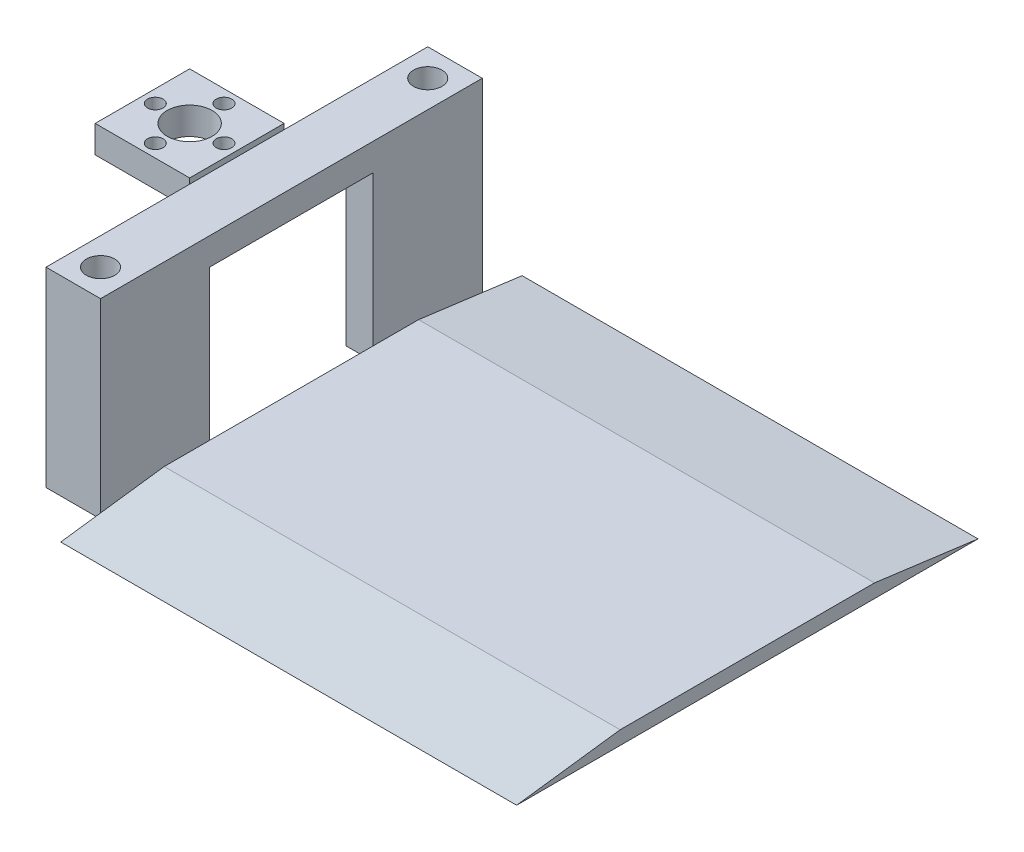
SolidWorks part; units mm, degrees
ref_plane "Front Plane" through (0, 0, 0) normal (0, 0, 1) x (1, 0, 0)
ref_plane "Top Plane" through (0, 0, 0) normal (0, 1, 0) x (1, 0, 0)
ref_plane "Right Plane" through (0, 0, 0) normal (1, 0, 0) x (0, 0, -1)
sketch "Sketch1" plane through (0, 0, 0) normal (0, 1, 0) x (1, 0, 0)
  line L1 (0, 0) -> (106.172, 0)
  line L2 (0, 0) -> (0, 107.442)
  line L3 (0, 107.442) -> (106.172, 107.442)
  line L4 (106.172, 0) -> (106.172, 107.442)
  dimension "D1" = 107.442
  dimension "D2" = 106.172
extrude "Boss-Extrude1" add sketch "Sketch1" along normal blind 3.175
sketch "Sketch3" plane through (0, 0, 0) normal (0, 1, 0) x (1, 0, 0)
  line L0 (0, 53.721) -> (106.172, 53.721) construction
  line L5 (-12.7, 85.471) -> (0, 85.471)
  line L6 (-12.7, 85.471) -> (-12.7, 98.171)
  line L7 (-12.7, 98.171) -> (0, 98.171)
  line L8 (0, 85.471) -> (0, 98.171)
  line L9 (-12.7, 85.471) -> (0, 98.171) construction
  line L10 (-12.7, 98.171) -> (0, 85.471) construction
  line L11 (0, 107.442) -> (0, 0) construction
  line L12 (106.172, 0) -> (106.172, 107.442) construction
  line L13 (-12.7, 9.271) -> (0, 21.971) construction
  line L14 (-12.7, 21.971) -> (0, 9.271) construction
  line L15 (0, 21.971) -> (0, 9.271)
  line L16 (-12.7, 9.271) -> (0, 9.271)
  line L17 (-12.7, 21.971) -> (-12.7, 9.271)
  line L18 (-12.7, 21.971) -> (0, 21.971)
  circle A1 centre (-6.35, 91.821) radius 3.302
  circle A2 centre (-6.35, 15.621) radius 3.302
  point P0 (-6.35, 91.821)
  point P21 (-6.35, 15.621)
  dimension "D2" = 6.604
  dimension "D1" = 12.7
  dimension "D3" = 12.7
  dimension "D4" = 76.2
extrude "Boss-Extrude2" add sketch "Sketch3" along normal blind 44.45
sketch "Sketch4" plane through (106.172, 0, 0) normal (1, 0, 0) x (0, 0, -1)
  line L5 (0, 0) -> (24.0965, 3.175)
  line L7 (0, 3.175) -> (107.442, 3.175) construction
  line L8 (24.0965, 3.175) -> (0, 3.175)
  line L9 (0, 3.175) -> (0, 0)
  line L10 (53.721, 3.175) -> (53.721, 0) construction
  line L11 (0, 0) -> (107.442, 0) construction
  line L12 (107.442, 3.175) -> (107.442, 0)
  line L13 (83.3455, 3.175) -> (107.442, 3.175)
  line L14 (107.442, 0) -> (83.3455, 3.175)
extrude "Cut-Extrude1" cut sketch "Sketch4" against normal up to surface (106.172 mm away) up to face at (0, 23.8125, -15.621)
sketch "Sketch6" plane through (0, 0, -85.471) normal (0, 0, 1) x (1, 0, 0)
  line L0 (0, 44.45) -> (0, 2.8949) construction
  line L1 (-12.7, 44.45) -> (0, 44.45)
  line L2 (-12.7, 44.45) -> (-12.7, 38.1)
  line L3 (-12.7, 38.1) -> (0, 38.1)
  line L4 (0, 44.45) -> (0, 38.1)
  dimension "D1" = 6.35
extrude "Boss-Extrude3" add sketch "Sketch6" along normal up to surface (63.5 mm away) up to face at (-5.08, 18.359, -21.971)
sketch "Sketch11" plane through (0, 44.45, 0) normal (0, 1, 0) x (1, 0, 0)
  line L0 (-12.7, 98.171) -> (-12.7, 9.271) construction
  line L1 (-12.7, 64.721) -> (-34.7, 64.721)
  line L2 (-12.7, 64.721) -> (-12.7, 42.721)
  line L3 (-12.7, 42.721) -> (-34.7, 42.721)
  line L4 (-34.7, 64.721) -> (-34.7, 42.721)
  line L5 (0, 53.721) -> (-28.0072, 53.721) construction
  line L6 (-12.7, 64.721) -> (-34.7, 42.721) construction
  line L7 (-34.7, 64.721) -> (-12.7, 42.721) construction
  line L9 (0, 9.271) -> (0, 98.171) construction
  circle A0 centre (-23.7, 53.721) radius 5.227
  circle A1 centre (-23.7, 61.721) radius 1.8135
  circle A2 centre (-15.7, 53.721) radius 1.8135
  circle A3 centre (-23.7, 45.721) radius 1.8135
  circle A4 centre (-31.7, 53.721) radius 1.8135
  point P22 (-23.7, 53.721)
  dimension "D4" = 10.454
  dimension "D3" = 3.627
  dimension "D1" = 22
  dimension "D2" = 22
  dimension "D5" = 8
  dimension "D6" = 4
extrude "Boss-Extrude5" add sketch "Sketch11" against normal blind 6.35 from offset 1.27
sketch "Sketch12" plane through (0, 0, 0) normal (0, -1, 0) x (1, 0, 0)
  line L5 (0, -85.471) -> (0, -21.971) construction
  line L6 (0, -34.671) -> (-6.35, -34.671)
  line L7 (0, -34.671) -> (0, -21.971)
  line L8 (0, -21.971) -> (-6.35, -21.971)
  line L9 (-6.35, -34.671) -> (-6.35, -21.971)
  line L10 (0, -21.971) -> (-12.7, -21.971) construction
  line L11 (106.172, -53.721) -> (-53.2514, -53.721) construction
  line L12 (106.172, 0) -> (106.172, -107.442) construction
  line L13 (-6.35, -72.771) -> (-6.35, -85.471)
  line L14 (0, -85.471) -> (-6.35, -85.471)
  line L15 (0, -72.771) -> (0, -85.471)
  line L16 (0, -72.771) -> (-6.35, -72.771)
  dimension "D1" = 38.1
extrude "Boss-Extrude6" add sketch "Sketch12" against normal up to surface (38.1 mm away) up to face at (-6.35, 38.1, -53.721)
equation "\"tightTol\" = 0.005in"
equation "\"normTol\"= 0.01in"
equation "\"looseTol\"= 0.02in"
equation "\"4.250000in-\"= 4.25"
equation "\"D1@Sketch1\"=4.25-\"looseTol\""
equation "\"D2@Sketch3\"=\"normTol\"+0.250000in"
equation "\"D4@Sketch11\"=\"normTol\"+10.2mm"
equation "\"D2@Sketch1\"=4.200000in-\"looseTol\""
equation "\"D1@Sketch11\"=22mm"
equation "\"D2@Sketch11\"=22mm"
equation "\"D3@Sketch11\"=3.5mm+\"tightTol\""
equation "\"D5@Sketch11\"=8mm"
